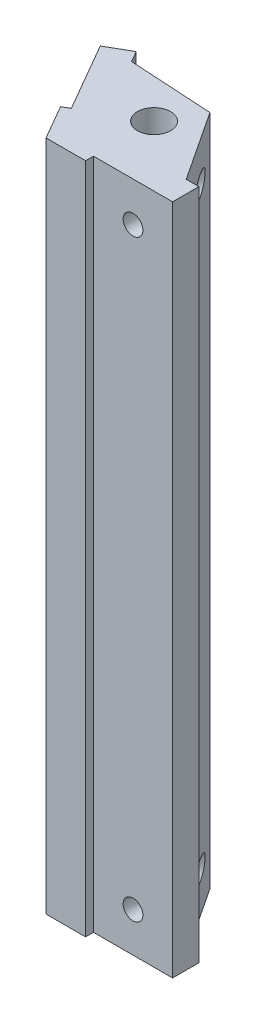
SolidWorks part; units mm, degrees
material "6061-T6 (SS)"
ref_plane "Front Plane" through (0, 0, 0) normal (0, 0, 1) x (1, 0, 0)
ref_plane "Top Plane" through (0, 0, 0) normal (0, 1, 0) x (1, 0, 0)
ref_plane "Right Plane" through (0, 0, 0) normal (1, 0, 0) x (0, 0, -1)
sketch "Sketch1" plane through (0, 0, 0) normal (0, 1, 0) x (1, 0, 0)
  line L0 (0, 0) -> (15, 0)
  line L1 (0, 0) -> (-7.5, 12.9904)
  line L2 (15, 0) -> (15, 4.3301)
  line L3 (0, 0) -> (2.5, 4.3301) construction
  line L4 (15, 4.3301) -> (13.3979, 4.3301)
  line L5 (-2.949, 13.768) -> (-3.75, 15.1554)
  line L6 (-3.75, 15.1554) -> (-7.5, 12.9904)
  line L7 (-2.949, 13.768) -> (7.5874, 13.1418)
  line L8 (7.5874, 13.1418) -> (13.3979, 4.3301)
  line L9 (2.5, 4.3301) -> (7.5874, 13.1418) construction
  line L10 (-2.949, 13.768) -> (2.5, 4.3301) construction
  line L11 (2.5, 4.3301) -> (13.3979, 4.3301) construction
  dimension "D1" = 5
  dimension "D2" = 15
  dimension "D3" = 240
extrude "Boss-Extrude1" add sketch "Sketch1" along normal blind 85
sketch "Sketch3" plane through (0, 85, 0) normal (0, 1, 0) x (1, 0, 0)
  line L0 (-7.5, 12.9904) -> (-6.634, 13.4904)
  line L1 (-3.75, 15.1554) -> (-7.5, 12.9904) construction
  line L2 (-6.634, 13.4904) -> (-1.634, 4.8301)
  line L3 (-1.634, 4.8301) -> (-2.5, 4.3301)
  line L4 (-7.5, 12.9904) -> (0, 0) construction
  line L5 (-2.5, 4.3301) -> (-7.5, 12.9904)
  line L6 (15, 0) -> (15, 1)
  line L7 (15, 0) -> (15, 4.3301) construction
  line L8 (15, 1) -> (5, 1)
  line L9 (5, 1) -> (5, 0)
  line L11 (5, 0) -> (15, 0)
  line L12 (0, 0) -> (15, 0) construction
  dimension "D1" = 1
  dimension "D2" = 5
extrude "Cut-Extrude1" cut sketch "Sketch3" against normal through all
sketch "Sketch4" plane through (0, 85, 0) normal (0, 1, 0) x (1, 0, 0)
  line L0 (0, 0) -> (7.5874, 13.1418) construction
  point P4 (5, 8.6603)
  dimension "D1" = 10
hole_wizard "M5x0.8 Tapped Hole1" positions "Sketch6" profile "Sketch7" tap size "M5x0.8" standard "ANSI Metric"
sketch "Sketch6" plane through (0, 85, 0) normal (0, 1, 0) x (1, 0, 0)
  point P0 (5, 8.6603)
sketch "Sketch7" plane through (5, 85, -8.6603) normal (1, 0, 0) x (0, 0, 1)
  line L0 (0, 0) -> (0, 17.2618)
  line L1 (0, 17.2618) -> (2.1, 16)
  line L2 (2.1, 16) -> (2.1, 0)
  line L5 (2.1, 0) -> (0, 0)
  line L10 (0, 17.2618) -> (-2.1, 16) construction
  line L11 (0, -6.35) -> (0, 107.95) construction
  dimension "Tap Drill Dia." = 4.2
  dimension "Tap Drill Depth" = 16
  dimension "Drill Angle" = 118
cosmetic thread "Hole Thread1" parameters "D1"=14, "D2"=5
ref_point "Point1"
hole_wizard "M5x0.8 Tapped Hole2" positions "Sketch11" profile "Sketch10" tap size "M5x0.8" standard "ANSI Metric"
sketch "Sketch11" plane through (0, 0, 0) normal (0, -1, 0) x (-1, 0, 0)
  point P0 (-5, 8.6603)
sketch "Sketch10" plane through (5, 0, -8.6603) normal (1, 0, 0) x (0, 0, -1)
  line L0 (0, 0) -> (0, 17.6618)
  line L1 (0, 17.6618) -> (2.1, 16.4)
  line L2 (2.1, 16.4) -> (2.1, 0)
  line L5 (2.1, 0) -> (0, 0)
  line L10 (0, 17.6618) -> (-2.1, 16.4) construction
  line L11 (0, -6.35) -> (0, 107.95) construction
  dimension "Tap Drill Dia." = 4.2
  dimension "Tap Drill Depth" = 16.4
  dimension "Drill Angle" = 118
cosmetic thread "Hole Thread2" parameters "D1"=14, "D2"=5
sketch "Sketch12" plane through (0.866, 0, -0.5) normal (-0.866, 0, 0.5) x (0.5, 0, 0.866)
  line L0 (-15, 42.5) -> (-5, 42.5) construction
  line L1 (-15, 0) -> (-15, 85) construction
  line L2 (-5, 0) -> (-5, 85) construction
  line L3 (-10, 80) -> (-10, 5) construction
  point P8 (-10, 42.5)
  dimension "D1" = 75
hole_wizard "M3x0.5 Tapped Hole1" positions "Sketch14" profile "Sketch13" tap size "M3x0.5" standard "ANSI Metric" end condition through all
sketch "Sketch14" plane through (0.866, 0, -0.5) normal (-0.866, 0, 0.5) x (0.5, 0, 0.866)
  point P0 (-10, 80)
  point P3 (-10, 5)
sketch "Sketch13" plane through (-4.134, 80, -9.1603) normal (0, 1, 0) x (0.5, 0, 0.866)
  line L0 (0, 0) -> (0, 19.5681)
  line L1 (0, 19.5681) -> (1.25, 19.5681)
  line L2 (1.25, 19.5681) -> (1.25, 0)
  line L5 (1.25, 0) -> (0, 0)
  line L11 (0, -6.35) -> (0, 107.95) construction
  dimension "Thru Tap Drill Dia." = 2.5
  dimension "Thru Tap Drill Depth" = 19.5681
cosmetic thread "Hole Thread3" parameters "D2"=3
cosmetic thread "Hole Thread4" parameters "D2"=3
sketch "Sketch15" plane through (0, 0, -1) normal (0, 0, 1) x (1, 0, 0)
  line L0 (5, 42.5) -> (15, 42.5) construction
  line L1 (5, 0) -> (5, 85) construction
  line L2 (15, 0) -> (15, 85) construction
  line L3 (10, 80) -> (10, 5) construction
  point P8 (10, 42.5)
  dimension "D1" = 75
hole_wizard "M3x0.5 Tapped Hole2" positions "Sketch17" profile "Sketch16" tap size "M3x0.5" standard "ANSI Metric" end condition through all
sketch "Sketch17" plane through (0, 0, -1) normal (0, 0, 1) x (1, 0, 0)
  point P0 (10, 80)
  point P3 (10, 5)
sketch "Sketch16" plane through (10, 80, -1) normal (1, 0, 0) x (0, -1, 0)
  line L0 (0, 0) -> (0, 14.1554)
  line L1 (0, 14.1554) -> (1.25, 14.1554)
  line L2 (1.25, 14.1554) -> (1.25, 0)
  line L5 (1.25, 0) -> (0, 0)
  line L11 (0, -6.35) -> (0, 107.95) construction
  dimension "Thru Tap Drill Dia." = 2.5
  dimension "Thru Tap Drill Depth" = 14.1554
cosmetic thread "Hole Thread5" parameters "D2"=3
cosmetic thread "Hole Thread6" parameters "D2"=3
